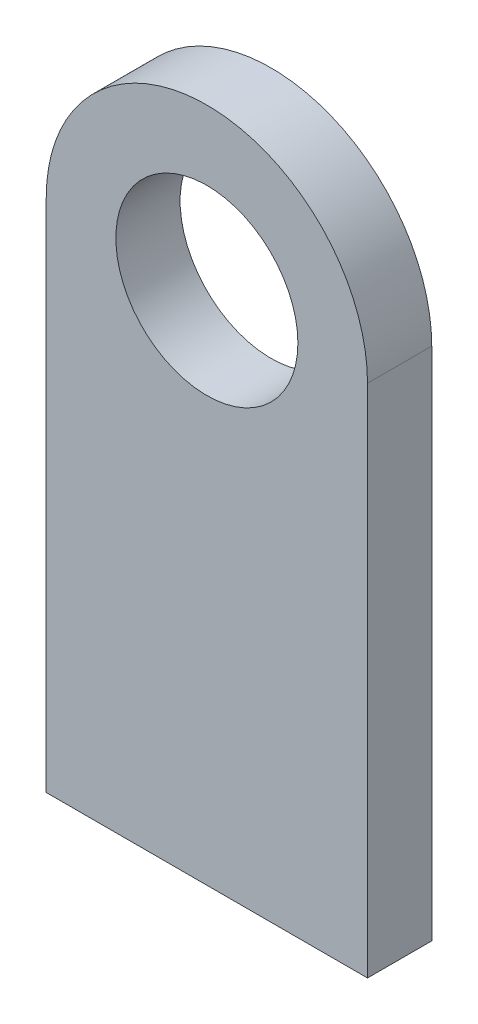
SolidWorks part; units mm, degrees
ref_plane "Front Plane" through (0, 0, 0) normal (0, 0, 1) x (1, 0, 0)
ref_plane "Top Plane" through (0, 0, 0) normal (0, 1, 0) x (1, 0, 0)
ref_plane "Right Plane" through (0, 0, 0) normal (1, 0, 0) x (0, 0, -1)
sketch "Sketch1" plane through (0, 0, 0) normal (0, 0, 1) x (1, 0, 0)
  line L0 (-15, 0) -> (-15, 48.1)
  line L1 (15, 48.1) -> (15, 0)
  line L2 (15, 0) -> (-15, 0)
  circle A0 centre (0, 48.1) radius 8.5
  arc A1 (-15, 48.1) -> (15, 48.1) centre (0, 48.1) cw
  point P7 (0, 0)
  dimension "D1" = 17
  dimension "D2" = 48.1
  dimension "D3" = 30
extrude "Boss-Extrude1" add sketch "Sketch1" along normal blind 6
